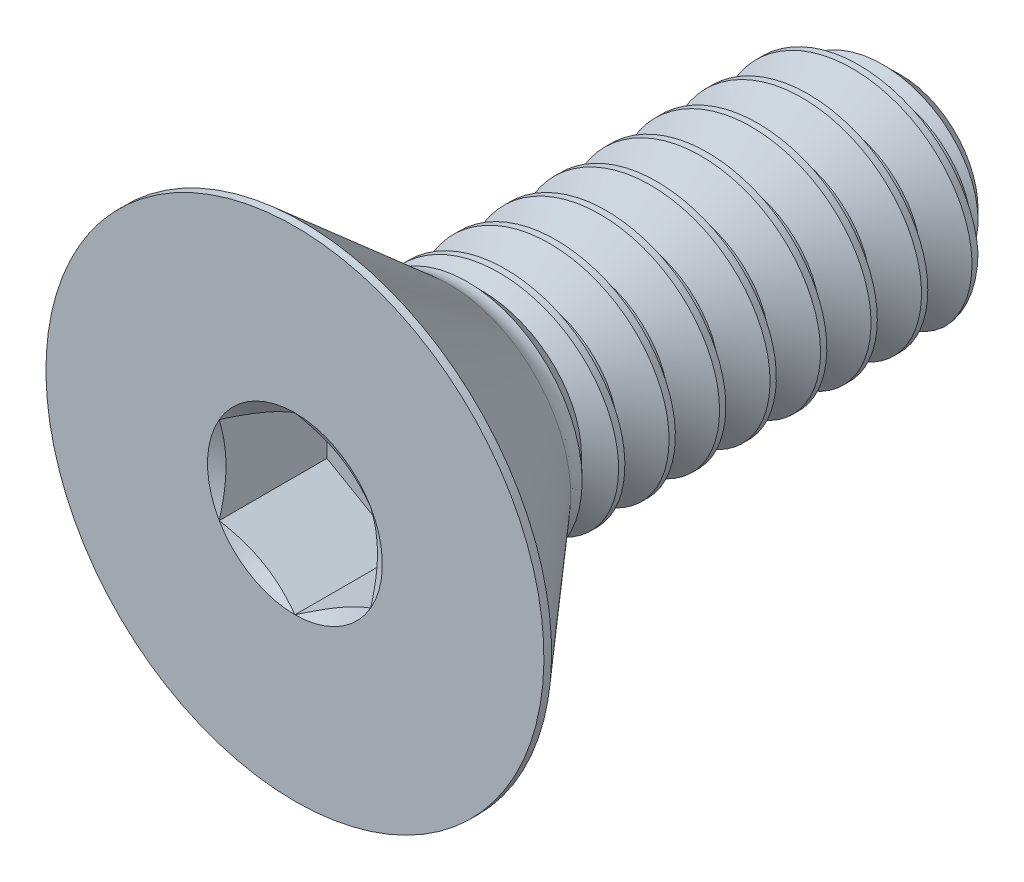
SolidWorks part; units mm, degrees
material "Plain Carbon Steel"
ref_plane "Front" through (0, 0, 0) normal (0, 0, 1) x (1, 0, 0)
ref_plane "Top" through (0, 0, 0) normal (0, 1, 0) x (1, 0, 0)
ref_plane "Right" through (0, 0, 0) normal (1, 0, 0) x (0, 0, -1)
sketch "Sketch1" plane through (0, 0, 0) normal (1, 0, 0) x (0, 0, -1)
  line L0 (0, 5.2197) -> (0.1613, 5.2197) construction
  line L1 (0.1613, 5.2197) -> (3.2258, 2.5558) construction
  line L2 (0, 2.413) -> (12.7, 2.413)
  line L3 (12.7, 2.413) -> (12.7, 0)
  line L4 (12.7, 0) -> (0, 0)
  line L5 (0, 0) -> (0, 5.2197) construction
  line L6 (0, 5.2197) -> (0, -5.2197) construction
  line L7 (12.7, 2.413) -> (12.7, -2.413) construction
  line L8 (0, -5.2197) -> (0.1613, -5.2197) construction
  line L9 (0.1613, -5.2197) -> (3.2258, -2.5558) construction
  line L11 (0, 2.413) -> (0, 0)
  line L12 (3.6076, 2.413) -> (3.6076, 0) construction
  line L13 (-12.7, 0) -> (-12.7, 2.413) construction
  arc A1 (3.2258, 2.5558) -> (3.6076, 2.413) centre (3.6076, 2.995) ccw construction
  dimension "D1" = 0.1613
  dimension "Head Ht" = 3.2258
  dimension "Head Dia" = 10.4394
  dimension "Dia" = 4.826
  dimension "Lg" = 12.7
  dimension "Head Angle" = 82
  dimension "Min Thread" = 25.4
revolve "Revolve1" add sketch "Sketch1" angle 360 mid plane about L4
sketch "Sketch3" plane through (0, 0, -12.7) normal (0, 0, -1) x (-1, 0, 0)
  circle A0 centre (0, 0) radius 2.413
curve "Helix/Spiral1" pitch 1.0583 height 12.7 radius 2.413 centre (0, 0, -12.7) axis (0, 0, 1) start towards (0, 1, 0)
sketch "Sketch2" plane through (0, 0, 0) normal (1, 0, 0) x (0, 0, -1)
  line L0 (12.7, 2.413) -> (13.626, 2.413)
  line L1 (13.626, 2.413) -> (13.2292, 1.7256)
  line L2 (13.2292, 1.7256) -> (13.0969, 1.7256)
  line L3 (13.0969, 1.7256) -> (12.7, 2.413)
  line L4 (12.8984, 2.0693) -> (13.4276, 2.0693) construction
  dimension "D1" = 60
  dimension "D2" = 0.1323
  dimension "D3" = 0.5292
ref_plane "Plane2" through (0, 0, 12.7) normal (0, 0, 1) x (1, 0, 0)
chamfer "Chamfer1" distance 0.7937 angle 45 1 edges at (0, 2.413, -12.7)
sweep "Cut-Sweep1" cut profiles "Sketch2" path "Helix/Spiral1"
sketch "Sketch7" plane through (0, 0, 0) normal (1, 0, 0) x (0, 0, -1)
  line L0 (0, 5.2197) -> (0.1613, 5.2197) construction
  line L1 (0.1613, 5.2197) -> (3.2258, 2.5558) construction
  line L2 (0, 5.2197) -> (0.1613, 5.2197)
  line L3 (0.1613, 5.2197) -> (3.2258, 2.5558)
  line L4 (3.6076, 2.413) -> (3.6076, 0) construction
  line L5 (3.6076, 2.413) -> (3.6076, 0)
  line L7 (0, 0) -> (0, 5.2197) construction
  line L8 (0, 0) -> (0, 5.2197)
  line L9 (0, 0) -> (3.6076, 0)
  line L10 (5.7417, 0) -> (-5.7417, 0) construction
  arc A0 (3.2258, 2.5558) -> (3.6076, 2.413) centre (3.6076, 2.995) ccw construction
  arc A1 (3.2258, 2.5558) -> (3.6076, 2.413) centre (3.6076, 2.995) ccw
revolve "Revolve2" add sketch "Sketch7" angle 360 mid plane about L9
ref_plane "Plane1" through (0, 0, -3.6076) normal (0, 0, 1) x (1, 0, 0)
sketch "Sketch8" plane through (0, 0, -3.6076) normal (0, 0, 1) x (1, 0, 0)
  circle A0 centre (0, 0) radius 2.413
extrude "Boss-Extrude1" add sketch "Sketch8" against normal through all draft 46
sketch "Sketch5" plane through (0, 0, 0) normal (0, 0, 1) x (1, 0, 0)
  line L0 (0, 0) -> (-1.8331, 0) construction
  line L1 (0, 0) -> (-2.7496, 1.5875) construction
  line L2 (0, 0) -> (-2.7496, -1.5875) construction
  line L6 (0, 1.8331) -> (0, 1.5119) construction
  line L7 (0, 1.5119) -> (0, 1.1906) construction
  line L9 (0, 1.8331) -> (-1.5875, 0.9165)
  line L10 (-1.5875, 0.9165) -> (-1.5875, -0.9165)
  line L11 (-1.5875, -0.9165) -> (0, -1.8331)
  line L12 (0, -1.8331) -> (1.5875, -0.9165)
  line L13 (1.5875, -0.9165) -> (1.5875, 0.9165)
  line L14 (1.5875, 0.9165) -> (0, 1.8331)
  circle A0 centre (0, 0) radius 1.8331 construction
  circle A1 centre (0, 0) radius 1.5119 construction
  circle A2 centre (0, 0) radius 1.1906 construction
  circle A3 centre (0, 0) radius 1.5875 construction
  dimension "D3" = 2.3813
  dimension "Hex" = 3.175
  dimension "D4" = 30
  dimension "D5" = 30
extrude "Cut-Extrude2" cut sketch "Sketch5" against normal blind 2.2581
sketch "Sketch6" plane through (0, 0, 0) normal (0, 0, 1) x (1, 0, 0)
  circle A0 centre (0, 0) radius 1.8331
extrude "Cut-Extrude3" cut sketch "Sketch6" against normal blind 2.2581 draft 60
sketch "Sketch9" [suppressed] plane through (0, 0, -3.6076) normal (0, 0, 1) x (1, 0, 0)
  circle A1 centre (0, 0) radius 2.413
  circle A2 centre (0, 0) radius 2.413
  point P0 (0, 2.413)
  dimension "D1" = 0
extrude "Boss-Extrude2" [suppressed] add sketch "Sketch9" against normal up to surface (15.4424 mm away) up to plane "Plane2"
sketch "Sketch10" plane through (0, 0, 0) normal (1, 0, 0) x (0, 0, -1)
  line L0 (12.7, 2.413) -> (12.7, -2.413) construction
  point P0 (11.1125, -2.413)
  dimension "D1" = 1.5875
equation "\"D3@Helix/Spiral1\" = \"Lg@Sketch1\""
equation "\"D2@Sketch2\" = \"D4@Helix/Spiral1\" * .125"
equation "\"D3@Sketch2\" = \"D4@Helix/Spiral1\" * .5"
equation "\"D1@Chamfer1\" = \"D4@Helix/Spiral1\" * .75"
equation "\"D1@Cut-Extrude2\" = \"Head Ht@Sketch1\" * .7"
equation "\"D1@Sketch1\" = \"Head Ht@Sketch1\" * .05"
equation "\"D1@Sketch10\" = \"D4@Helix/Spiral1\" * 1.5"
equation "\"D1@Cut-Extrude3\" = \"D1@Cut-Extrude2\""
equation "\"D3@Sketch5\" = \"Hex@Sketch5\" * .75"
